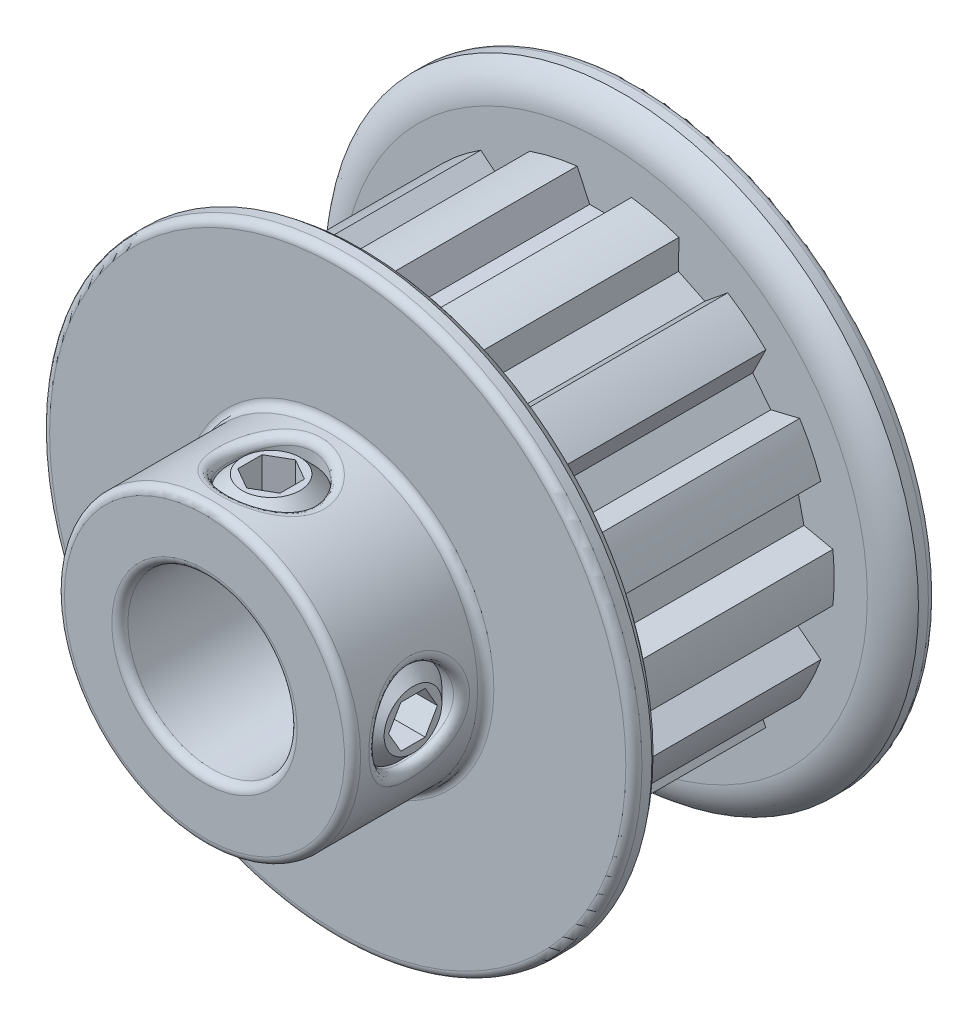
SolidWorks part; units mm, degrees
material "6061 Alloy"
ref_plane "Front Plane" through (0, 0, 0) normal (0, 0, 1) x (1, 0, 0)
ref_plane "Top Plane" through (0, 0, 0) normal (0, 1, 0) x (1, 0, 0)
ref_plane "Right Plane" through (0, 0, 0) normal (1, 0, 0) x (0, 0, -1)
sketch "Sketch1" plane through (0, 0, 0) normal (0, 0, 1) x (1, 0, 0)
  line L0 (-1.2827, 10.792) -> (-0.6905, 9.522)
  line L1 (-0.6905, 9.522) -> (0.6905, 9.522)
  line L2 (0.6905, 9.522) -> (1.2827, 10.792)
  line L3 (-1.2827, 10.792) -> (1.2827, 10.792)
  line L4 (0, 0) -> (0, 9.522) construction
  line L5 (0, 9.522) -> (0, 11.808) construction
  circle A0 centre (0, 0) radius 11.3 construction
  circle A1 centre (0, 0) radius 14 construction
  circle A2 centre (0, 0) radius 10.868 construction
  point P6 (0, 10.792)
  point P11 (0, 11.3)
  point P13 (0, 14)
  point P14 (0, 10.868)
  dimension "D1" = 1.016
  dimension "D2" = 0.508
sketch "Sketch2" plane through (0, 0, 0) normal (1, 0, 0) x (0, 0, -1)
  line L0 (-10.3, 4) -> (10.3, 4)
  line L1 (-10.3, 4) -> (-10.3, 7)
  line L2 (-10.3, 7) -> (-4, 7)
  line L3 (-4, 7) -> (-4, 14)
  line L4 (-4, 14) -> (-2.3, 14) construction
  line L5 (-2.3, 14) -> (-2.3, 10.868) construction
  line L6 (-2.3, 10.868) -> (8.6, 10.868)
  line L7 (8.6, 10.868) -> (8.6, 14) construction
  line L8 (8.6, 14) -> (10.3, 14) construction
  line L9 (10.3, 14) -> (10.3, 4)
  line L10 (-10.3, 0) -> (10.3, 0) construction
  line L13 (-4, 14) -> (-3.15, 14)
  line L14 (-2.3, 12.434) -> (-2.3, 10.868)
  line L15 (8.6, 10.868) -> (8.6, 12.434)
  line L16 (9.45, 14) -> (10.3, 14)
  arc A0 (-2.3, 12.434) -> (-3.15, 14) centre (-4.1676, 12.434) ccw
  arc A1 (8.6, 12.434) -> (9.45, 14) centre (10.4676, 12.434) cw
  point P12 (-2.3, 12.434)
  point P14 (-3.15, 14)
  point P20 (8.6, 12.434)
  point P21 (9.45, 14)
  point P25 (8.6, 0)
  point P26 (-2.3, 0)
  dimension "Bore" = 8
  dimension "Hub Dia" = 14
  dimension "Outside Width" = 14.3
  dimension "Inside Width" = 10.9
revolve "Revolve1" add sketch "Sketch2" angle 360 mid plane about L10
sketch "Sketch3" plane through (0, 0, 0) normal (0, 0, 1) x (1, 0, 0)
  line L0 (-0.6905, 9.522) -> (0.6905, 9.522) construction
  line L1 (0.6905, 9.522) -> (1.2827, 10.792) construction
  line L2 (-1.2827, 10.792) -> (-0.6905, 9.522) construction
  line L3 (-0.6905, 9.522) -> (0.6905, 9.522)
  line L4 (0.6905, 9.522) -> (1.2827, 10.792)
  line L5 (-1.2827, 10.792) -> (-0.6905, 9.522)
  circle A0 centre (0, 0) radius 10.868 construction
  arc A1 (1.2827, 10.792) -> (-1.2827, 10.792) centre (0, 0) ccw
extrude "Cut-Extrude1" cut sketch "Sketch3" against normal up to vertex (8.6 mm away) from vertex up to point (0, 10.868, -8.6) starting at point (0, 10.868, 2.3)
pattern_circular "CirPattern1" count 14 over 360 about axis through (0, 0, 10.3) along (0, 0, 1) of "Cut-Extrude1"
sketch "Sketch4" plane through (0, 0, 0) normal (0, 1, 0) x (1, 0, 0)
  line L0 (0, -4) -> (0, -10.3) construction
  line L1 (-7, -4) -> (7, -4) construction
  line L2 (-7, -10.3) -> (7, -10.3) construction
  circle A0 centre (0, -7.15) radius 2
  dimension "D1" = 4
extrude "Cut-Extrude2" cut sketch "Sketch4" along normal through all
ref_plane "Plane1" through (0, 0, 7.15) normal (0, 0, 1) x (1, 0, 0)
sketch "Sketch5" plane through (0, 0, 7.15) normal (0, 0, 1) x (1, 0, 0)
  line L0 (0, 0) -> (0, 7) construction
  line L1 (-2, 6.7082) -> (-2, 3.4641) construction
  line L2 (-2, 6.7082) -> (-2, 3.4641) construction
  line L3 (0, 6.7082) -> (0, 4)
  line L4 (0, 4) -> (-1.365, 4)
  line L5 (-2, 6.0732) -> (-2, 4.635)
  line L6 (-1.365, 6.7082) -> (0, 6.7082)
  line L7 (-2, 6.0732) -> (-1.365, 6.7082)
  line L8 (-2, 4.635) -> (-1.365, 4)
  circle A0 centre (0, 0) radius 7 construction
  circle A3 centre (0, 0) radius 4 construction
  point P13 (-2, 4)
  point P15 (-2, 6.7082)
revolve "Revolve2" add sketch "Sketch5" angle 360 mid plane about L0
sketch "Sketch6" plane through (0, 6.7082, 0) normal (0, -1, 0) x (-1, 0, 0)
  line L1 (0, -5.9953) -> (-1, -6.5726)
  line L2 (-1, -6.5726) -> (-1, -7.7274)
  line L3 (-1, -7.7274) -> (0, -8.3047)
  line L4 (0, -8.3047) -> (1, -7.7274)
  line L5 (1, -7.7274) -> (1, -6.5726)
  line L6 (1, -6.5726) -> (0, -5.9953)
  circle A0 centre (0, -7.15) radius 1 construction
  dimension "D1" = 2
extrude "Cut-Extrude3" cut sketch "Sketch6" along normal blind 1.5
pattern_circular "CirPattern2" count 2 every 90 of "Cut-Extrude2", "Revolve2", "Cut-Extrude3" reverse direction yes
fillet "Fillet1" radius 0.381 8 edges at (6.9902, -0.3708, 9.1153) (0.3708, 6.9902, 9.1153) (7, 0, 10.3) (4, 0, 10.3) (14, 0, 4) (7, 0, 4) (4, 0, -10.3) (14, 0, -10.3)
ref_axis "Center Axis 1" through (0, 0, -9.919) along (0, 0, 1)
ref_plane "Contact Plane 2" through (0, 0, 10.3) normal (0, 0, 1) x (1, 0, 0)
ref_plane "Contact Plane 3" through (0, 0, -10.3) normal (0, 0, -1) x (-1, 0, 0)
equation "\"D2@Sketch1\" = \"D1@Sketch1\"/2"
equation "\"D1@Sketch4\" = \"Bore@Sketch2\"/2"
equation "\"D1@Sketch6\" = \"D1@Sketch4\"/2"
equation "\"D1@Cut-Extrude3\" = \"D1@Sketch6\"*.75"
